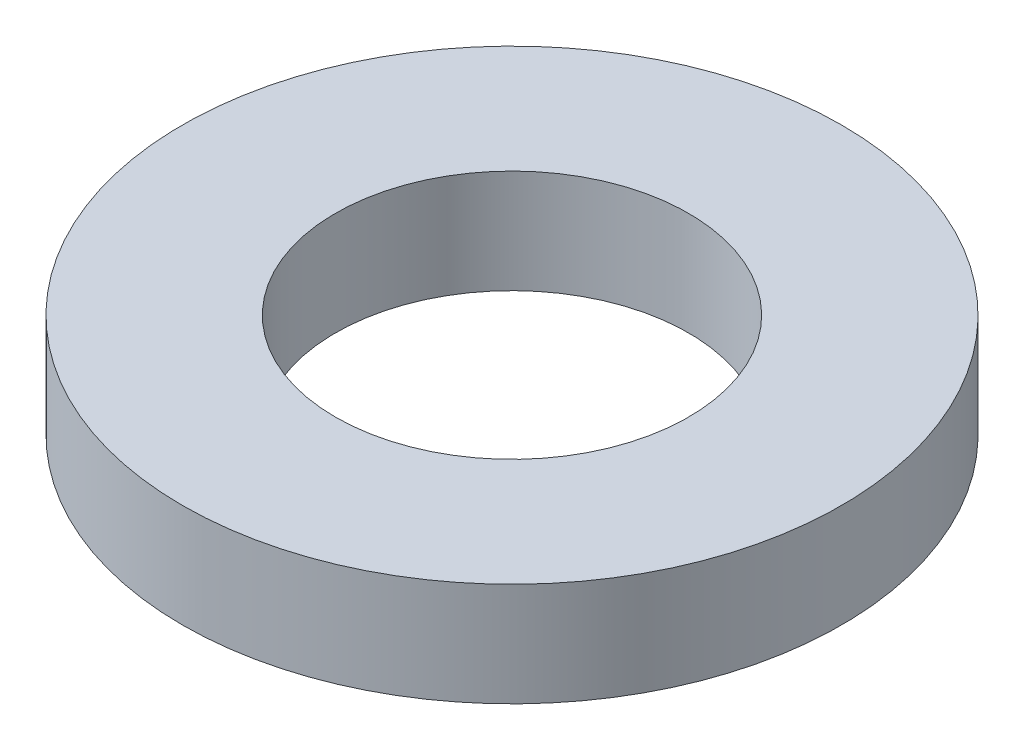
SolidWorks part; units mm, degrees
ref_plane "Front Plane" through (0, 0, 0) normal (0, 0, 1) x (1, 0, 0)
ref_plane "Top Plane" through (0, 0, 0) normal (0, 1, 0) x (1, 0, 0)
ref_plane "Right Plane" through (0, 0, 0) normal (1, 0, 0) x (0, 0, -1)
sketch "Sketch1" plane through (0, 0, 0) normal (0, 1, 0) x (1, 0, 0)
  circle A0 centre (0, 0) radius 70
  dimension "FLANGE_OD" = 140
extrude "Boss-Extrude1" add sketch "Sketch1" along normal blind 22
sketch "Sketch2" plane through (0, 0, 0) normal (0, 1, 0) x (1, 0, 0)
  circle A0 centre (0, 0) radius 37.5
  dimension "BORE_D" = 75
extrude "Cut-Extrude1" cut sketch "Sketch2" along normal through all
sketch "Sketch3" plane through (0, 22, 0) normal (0, 1, 0) x (1, 0, 0)
  circle A0 centre (0, 0) radius 29.0057 construction
  circle A1 centre (-29.0057, 0) radius 5.5269
  dimension "BOLT_D" = 11.0537
  dimension "BOLT_PCD" = 58.0114
extrude "Cut-Extrude2" cut sketch "Sketch3" against normal blind 20.4184 rebuild error yes
pattern_circular "CirPattern1" count 5 over 360 rebuild error yes
